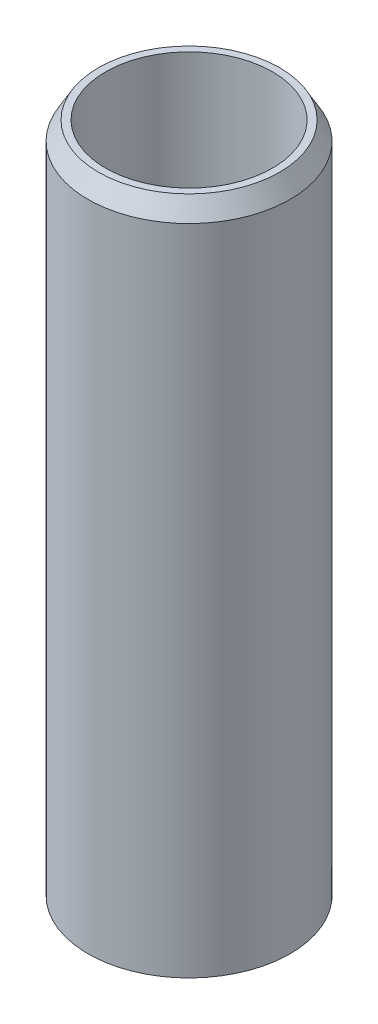
SolidWorks part; units mm, degrees
ref_plane "Front Plane" through (0, 0, 0) normal (0, 0, 1) x (1, 0, 0)
ref_plane "Top Plane" through (0, 0, 0) normal (0, 1, 0) x (1, 0, 0)
ref_plane "Right Plane" through (0, 0, 0) normal (1, 0, 0) x (0, 0, -1)
sketch "Sketch1" plane through (0, 0, 0) normal (0, 1, 0) x (1, 0, 0)
  circle A0 centre (0, 0) radius 32.5
  dimension "SHAFT_OD" = 65
extrude "Boss-Extrude1" add sketch "Sketch1" along normal blind 219.2337
sketch "Sketch2" plane through (0, 0, 0) normal (0, 1, 0) x (1, 0, 0)
  circle A0 centre (0, 0) radius 26.8329
  dimension "BORE_D" = 53.6657
extrude "Cut-Extrude1" cut sketch "Sketch2" along normal through all
chamfer "Chamfer1" distance 5.8672 angle 30 2 edges at (0, 219.2337, 32.5) (0, 0, 32.5) first distance on face at (0, 219.2337, 32.5) first distance on face at (0, 0, 26.8329)
